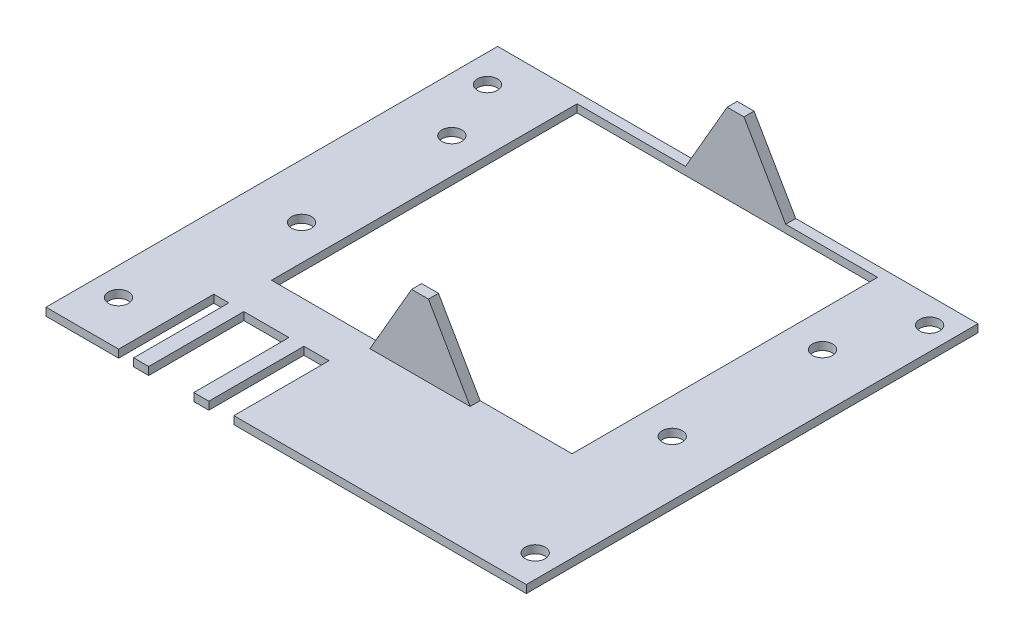
SolidWorks part; units mm, degrees
material "ABS"
ref_plane "Front Plane" through (0, 0, 0) normal (0, 0, 1) x (1, 0, 0)
ref_plane "Top Plane" through (0, 0, 0) normal (0, 1, 0) x (1, 0, 0)
ref_plane "Right Plane" through (0, 0, 0) normal (1, 0, 0) x (0, 0, -1)
sketch "Sketch1" plane through (0, 0, 0) normal (0, 1, 0) x (1, 0, 0)
  line L1 (-32.2441, 108.719) -> (64.6459, 108.719)
  line L2 (-32.2441, 108.719) -> (-32.2441, 18.549)
  line L3 (-32.2441, 18.549) -> (64.6459, 18.549)
  line L4 (64.6459, 108.719) -> (64.6459, 18.549)
  dimension "D1" = 96.89
  dimension "D2" = 90.17
extrude "PCB" add sketch "Sketch1" along normal blind 1.57
sketch "Sketch2" plane through (0, 1.57, 0) normal (0, 1, 0) x (1, 0, 0)
  line L0 (64.6459, 18.549) -> (64.6459, 108.719) construction
  line L1 (-32.2441, 18.549) -> (64.6459, 18.549) construction
  circle A0 centre (59.5659, 24.899) radius 2
  circle A1 centre (-26.1641, 27.439) radius 2
  circle A2 centre (-26.1641, 101.099) radius 2
  circle A3 centre (59.5659, 103.639) radius 2
  dimension "D3" = 4
  dimension "D6" = 4
  dimension "D11" = 4
  dimension "D12" = 4
  dimension "D1" = 5.08
  dimension "D2" = 6.35
  dimension "D4" = 90.81
  dimension "D5" = 8.89
  dimension "D7" = 90.81
  dimension "D8" = 5.08
  dimension "D9" = 85.09
  dimension "D10" = 82.55
extrude "M3 Mounting Holes" cut sketch "Sketch2" against normal blind 1.57
sketch "Sketch3" plane through (0, 1.57, 0) normal (0, 1, 0) x (1, 0, 0)
  line L0 (64.6459, 108.719) -> (-32.2441, 108.719) construction
  line L1 (12.7559, 108.719) -> (22.7559, 108.719)
  line L2 (12.7559, 108.719) -> (12.7559, 106.719)
  line L3 (12.7559, 106.719) -> (22.7559, 106.719)
  line L4 (22.7559, 108.719) -> (22.7559, 106.719)
  line L5 (-32.2441, 108.719) -> (-32.2441, 18.549) construction
  line L7 (12.7559, 45.719) -> (22.7559, 45.719)
  line L8 (12.7559, 45.719) -> (12.7559, 43.719)
  line L9 (12.7559, 43.719) -> (22.7559, 43.719)
  line L10 (22.7559, 45.719) -> (22.7559, 43.719)
  dimension "D1" = 2
  dimension "D2" = 10
  dimension "D3" = 0
  dimension "D4" = 45
  dimension "D5" = 61
  dimension "D6" = 2
  dimension "D7" = 45
extrude "Boss-Extrude1" [suppressed] add sketch "Sketch3" along normal blind 10
sketch "Sketch4" plane through (0, 1.57, 0) normal (0, 1, 0) x (1, 0, 0)
  line L0 (64.6459, 108.719) -> (-32.2441, 108.719) construction
  line L1 (64.6459, 108.719) -> (-32.2441, 108.719) construction
  line L2 (-32.2441, 108.719) -> (-32.2441, 18.549) construction
  line L3 (64.6459, 108.719) -> (-32.2441, 108.719) construction
  circle A0 centre (-20.8941, 88.719) radius 2
  circle A1 centre (53.1059, 88.719) radius 2
  circle A2 centre (-20.8941, 58.719) radius 2
  circle A3 centre (53.1059, 58.719) radius 2
  dimension "D1" = 4
  dimension "D2" = 4
  dimension "D7" = 4
  dimension "D8" = 4
  dimension "D12" = 74
  dimension "D3" = 20
  dimension "D4" = 20
  dimension "D5" = 74
  dimension "D6" = 11.35
  dimension "D9" = 50
  dimension "D10" = 50
  dimension "D11" = 11.35
extrude "Cut-Extrude1" cut sketch "Sketch4" against normal blind 23
ref_plane "Plane1" through (0, 0, -45.719) normal (0, 0, 1) x (1, 0, 0)
sketch "Sketch7" plane through (0, 0, -45.719) normal (0, 0, 1) x (1, 0, 0)
  line L0 (27.7559, 1.57) -> (19.4384, 15.9764)
  line L1 (19.4384, 15.9764) -> (16.0735, 15.9764)
  line L2 (16.0735, 15.9764) -> (7.7559, 1.57)
  line L3 (7.7559, 1.57) -> (27.7559, 1.57)
  line L4 (-32.2441, 1.57) -> (64.6459, 1.57) construction
  dimension "D1" = 60
  dimension "D2" = 60
  dimension "D3" = 0
  dimension "D4" = 3.3649
  dimension "D5" = 20
  dimension "D6" = 5
ref_plane "Plane2" through (0, 0, -108.719) normal (0, 0, 1) x (1, 0, 0)
sketch "Sketch8" plane through (0, 0, -108.719) normal (0, 0, 1) x (1, 0, 0)
  line L0 (27.7559, 1.57) -> (19.4384, 15.9764) construction
  line L1 (19.4384, 15.9764) -> (16.0735, 15.9764) construction
  line L2 (16.0735, 15.9764) -> (7.7559, 1.57) construction
  line L3 (7.7559, 1.57) -> (27.7559, 1.57) construction
  line L4 (27.7559, 1.57) -> (19.4384, 15.9764)
  line L5 (19.4384, 15.9764) -> (16.0735, 15.9764)
  line L6 (16.0735, 15.9764) -> (7.7559, 1.57)
  line L7 (7.7559, 1.57) -> (27.7559, 1.57)
extrude "Boss-Extrude2" add sketch "Sketch7" along normal blind 2
extrude "Boss-Extrude3" add sketch "Sketch8" along normal blind 2
sketch "Sketch9" plane through (0, 1.57, 0) normal (0, 1, 0) x (1, 0, 0)
  line L0 (-32.2441, 18.549) -> (64.6459, 18.549) construction
  line L1 (-14.2441, 18.549) -> (-17.2441, 18.549)
  line L2 (-14.2441, 18.549) -> (-14.2441, 37.549)
  line L3 (-14.2441, 37.549) -> (-17.2441, 37.549)
  line L4 (-17.2441, 18.549) -> (-17.2441, 37.549)
  line L5 (-32.2441, 108.719) -> (-32.2441, 18.549) construction
  line L6 (-11.2441, 18.549) -> (-2.2441, 18.549)
  line L7 (-11.2441, 18.549) -> (-11.2441, 37.549)
  line L8 (-11.2441, 37.549) -> (-2.2441, 37.549)
  line L9 (-2.2441, 18.549) -> (-2.2441, 37.549)
  line L11 (0.7559, 18.549) -> (5.7559, 18.549)
  line L12 (0.7559, 18.549) -> (0.7559, 37.549)
  line L13 (0.7559, 37.549) -> (5.7559, 37.549)
  line L14 (5.7559, 18.549) -> (5.7559, 37.549)
  dimension "D1" = 19
  dimension "D2" = 19
  dimension "D3" = 3
  dimension "D4" = 3
  dimension "D5" = 9
  dimension "D6" = 15
  dimension "D7" = 5
  dimension "D8" = 19
  dimension "D9" = 3
extrude "Cut-Extrude2" cut sketch "Sketch9" against normal through all
sketch "Sketch10" plane through (0, 1.57, 0) normal (0, 1, 0) x (1, 0, 0)
  line L0 (7.7559, 108.719) -> (-32.2441, 108.719) construction
  line L1 (-32.2441, 18.549) -> (-31.7441, 18.549)
  line L2 (-32.2441, 18.549) -> (-32.2441, 108.719)
  line L3 (-32.2441, 108.719) -> (-31.7441, 108.719)
  line L4 (-31.7441, 18.549) -> (-31.7441, 108.719)
  line L5 (64.6459, 108.719) -> (27.7559, 108.719) construction
  line L6 (64.6459, 18.549) -> (64.1459, 18.549)
  line L7 (64.6459, 18.549) -> (64.6459, 108.719)
  line L8 (64.6459, 108.719) -> (64.1459, 108.719)
  line L9 (64.1459, 18.549) -> (64.1459, 108.719)
  dimension "D1" = 0.5
  dimension "D2" = 0.5
extrude "Cut-Extrude3" cut sketch "Sketch10" against normal blind 10
sketch "Sketch11" plane through (0, 1.57, 0) normal (0, 1, 0) x (1, 0, 0)
  line L0 (7.7559, 106.719) -> (27.7559, 106.719) construction
  line L1 (-13.8941, 106.719) -> (46.1059, 106.719)
  line L2 (-13.8941, 106.719) -> (-13.8941, 45.719)
  line L3 (-13.8941, 45.719) -> (46.1059, 45.719)
  line L4 (46.1059, 106.719) -> (46.1059, 45.719)
  dimension "D1" = 60
  dimension "D2" = 61
  dimension "D3" = 0
  dimension "D4" = 7
extrude "Cut-Extrude4" cut sketch "Sketch11" against normal blind 10
